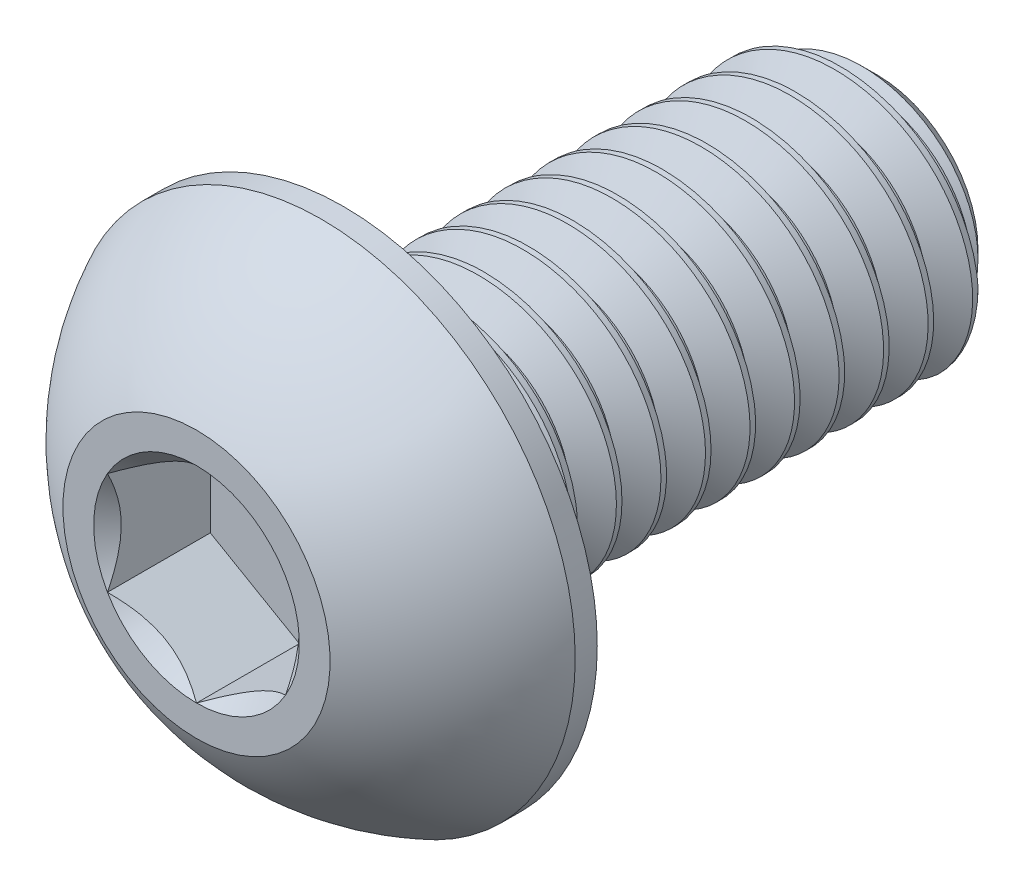
SolidWorks part; units mm, degrees
ref_plane "Front" through (0, 0, 0) normal (0, 0, 1) x (1, 0, 0)
ref_plane "Top" through (0, 0, 0) normal (0, 1, 0) x (1, 0, 0)
ref_plane "Right" through (0, 0, 0) normal (1, 0, 0) x (0, 0, -1)
sketch "Sketch1" plane through (0, 0, 0) normal (1, 0, 0) x (0, 0, -1)
  line L2 (1.65, 1.5) -> (7.65, 1.5)
  line L3 (7.65, 1.5) -> (7.65, 0)
  line L4 (7.65, 0) -> (1.65, 0)
  line L6 (1.4025, 2.85) -> (1.65, 2.85) construction
  line L7 (7.65, 1.5) -> (7.65, -1.5) construction
  line L8 (0, 0) -> (1.65, 0) construction
  line L9 (1.65, 2.85) -> (1.65, -2.85) construction
  line L11 (1.65, 1.5) -> (1.65, 0)
  line L13 (0, 1) -> (0, -1) construction
  line L14 (0, 1) -> (0, 1.5) construction
  arc A3 (0, 1.5) -> (1.4025, 2.85) centre (2.7948, 0) cw construction
  dimension "D1" = 0.2475
  dimension "Head Ht" = 1.65
  dimension "Head Dia" = 5.7
  dimension "Dia" = 3
  dimension "Lg" = 6
  dimension "Hex" = 2
revolve "Revolve1" add sketch "Sketch1" angle 360 mid plane about L4
sketch "Sketch3" plane through (0, 0, -7.65) normal (0, 0, -1) x (-1, 0, 0)
  circle A0 centre (0, 0) radius 1.5
curve "Helix/Spiral1" pitch 0.5 height 6.5 radius 1.5 centre (0, 0, -7.65) axis (0, 0, 1) start towards (0, 1, 0)
sketch "Sketch2" plane through (0, 0, 0) normal (1, 0, 0) x (0, 0, -1)
  line L0 (7.65, 1.5) -> (8.0875, 1.5)
  line L1 (8.0875, 1.5) -> (7.9, 1.1752)
  line L2 (7.9, 1.1752) -> (7.8375, 1.1752)
  line L3 (7.8375, 1.1752) -> (7.65, 1.5)
  line L4 (7.7438, 1.3376) -> (7.9938, 1.3376) construction
  dimension "D1" = 60
  dimension "D2" = 0.0625
  dimension "D3" = 0.25
chamfer "Chamfer1" distance 0.375 angle 45 1 edges at (0, 1.5, -7.65)
sweep "Cut-Sweep1" cut profiles "Sketch2" path "Helix/Spiral1"
sketch "Sketch7" plane through (0, 0, 0) normal (1, 0, 0) x (0, 0, -1)
  line L6 (1.4025, 2.85) -> (1.65, 2.85) construction
  line L8 (0, 0) -> (1.65, 0) construction
  line L11 (1.65, 2.85) -> (1.65, -2.85) construction
  line L12 (1.4025, 2.85) -> (1.65, 2.85)
  line L13 (0, 0) -> (1.65, 0)
  line L14 (0, 1) -> (0, -1) construction
  line L15 (1.65, 2.85) -> (1.65, 0)
  line L16 (0, 1.5) -> (0, 0)
  arc A2 (1.4025, 2.85) -> (0, 1.5) centre (2.7948, 0) ccw construction
  arc A3 (1.4025, 2.85) -> (0, 1.5) centre (2.7948, 0) ccw
revolve "Revolve2" add sketch "Sketch7" angle 360 mid plane about L13
sketch "Sketch5" plane through (0, 0, 0) normal (0, 0, 1) x (1, 0, 0)
  line L1 (1, -0.5774) -> (1, 0.5774)
  line L2 (1, 0.5774) -> (0, 1.1547)
  line L3 (0, 1.1547) -> (-1, 0.5774)
  line L4 (-1, 0.5774) -> (-1, -0.5774)
  line L5 (-1, -0.5774) -> (0, -1.1547)
  line L6 (0, -1.1547) -> (1, -0.5774)
  circle A0 centre (0, 0) radius 1 construction
extrude "Cut-Extrude2" cut sketch "Sketch5" against normal blind 1.155
sketch "Sketch6" plane through (0, 0, 0) normal (0, 0, 1) x (1, 0, 0)
  circle A0 centre (0, 0) radius 1.1547
extrude "Cut-Extrude3" cut sketch "Sketch6" against normal blind 1.155 draft 45
sketch "Sketch9" [suppressed] plane through (0, 0, -4.2164) normal (0, 0, 1) x (1, 0, 0)
  circle A2 centre (0, 0) radius 3.9687
extrude "Boss-Extrude2" [suppressed] add sketch "Sketch9" against normal offset from surface (9.525 mm away) 28.575 up to face at (0, 1.125, -7.65)
sketch "Sketch10" plane through (0, 0, 0) normal (1, 0, 0) x (0, 0, -1)
  line L0 (7.65, 1.5) -> (7.65, -1.5) construction
  point P0 (6.9, -1.5)
  dimension "D1" = 0.75
equation "\"D3@Helix/Spiral1\" = \"Lg@Sketch1\" + \"D4@Helix/Spiral1\""
equation "\"D2@Sketch2\" = \"D4@Helix/Spiral1\" * .125"
equation "\"D3@Sketch2\" = \"D4@Helix/Spiral1\" * .5"
equation "\"D1@Chamfer1\" = \"D4@Helix/Spiral1\" * .75"
equation "\"D1@Cut-Extrude2\" = \"Head Ht@Sketch1\" * .7"
equation "\"D1@Sketch1\" = \"Head Ht@Sketch1\" * .15"
equation "\"D1@Sketch10\" = \"D4@Helix/Spiral1\" * 1.5"
equation "\"D1@Cut-Extrude3\" = \"D1@Cut-Extrude2\""
